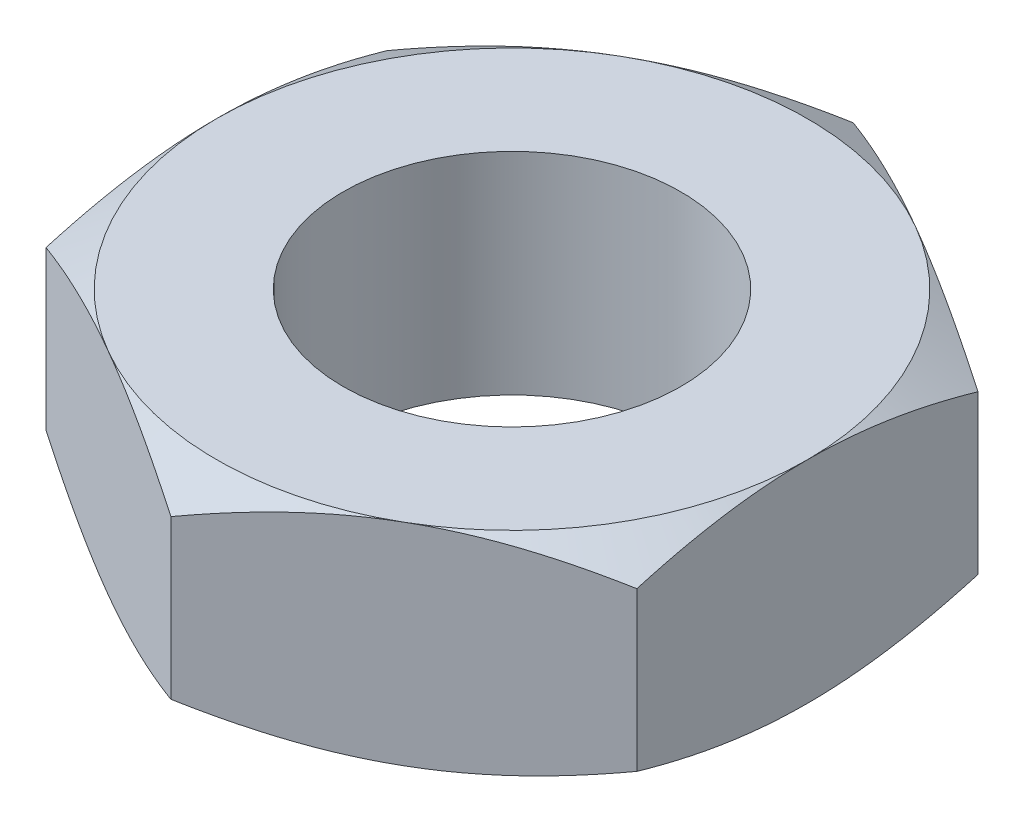
SolidWorks part; units mm, degrees
material "Alloy Steel"
ref_plane "Front Plane" through (0, 0, 0) normal (0, 0, 1) x (1, 0, 0)
ref_plane "Top Plane" through (0, 0, 0) normal (0, 1, 0) x (1, 0, 0)
ref_plane "Right Plane" through (0, 0, 0) normal (1, 0, 0) x (0, 0, -1)
sketch "Sketch1" plane through (0, 0, 0) normal (0, 1, 0) x (1, 0, 0)
  line L1 (-5.5563, 3.2079) -> (-5.5563, -3.2079)
  line L2 (-5.5563, -3.2079) -> (0, -6.4158)
  line L3 (0, -6.4158) -> (5.5562, -3.2079)
  line L4 (5.5562, -3.2079) -> (5.5562, 3.2079)
  line L5 (5.5562, 3.2079) -> (0, 6.4158)
  line L6 (0, 6.4158) -> (-5.5563, 3.2079)
  circle A0 centre (0, 0) radius 5.5563 construction
  circle A1 centre (0, 0) radius 3.175
  dimension "Thread Size" = 6.35
  dimension "Hex" = 11.1125
extrude "Boss-Extrude1" add sketch "Sketch1" along normal mid plane 3.9688
sketch "Sketch2" plane through (0, 1.9844, 0) normal (0, 1, 0) x (1, 0, 0)
  circle A0 centre (0, 0) radius 3.175 construction
  circle A1 centre (0, 0) radius 3.175
curve "Helix/Spiral1" [suppressed] pitch 0.9071 height 4.8759 turns 5.375 parameters "Pitch"=0.9071
sketch "Sketch3" plane through (0, 0, 0) normal (1, 0, 0) x (0, 0, -1)
  line L0 (2.5858, 2.4379) -> (3.175, 2.7781)
  line L1 (3.175, 2.7781) -> (3.175, 1.9844)
  line L2 (3.175, 1.9844) -> (2.5858, 2.3246)
  line L3 (2.5858, 2.3246) -> (2.5858, 2.4379)
  line L4 (2.8804, 2.608) -> (2.8804, 2.1545) construction
  line L5 (2.5858, 2.3812) -> (3.175, 2.3812) construction
  line L6 (3.175, 1.9844) -> (-3.175, 1.9844) construction
  dimension "D1" = 60
  dimension "D2" = 0.1134
  dimension "D3" = 0.4536
sweep "Sweep1" [suppressed] add profiles "Sketch3" path "Helix/Spiral1"
sketch "Sketch4" plane through (0, 1.9844, 0) normal (0, 1, 0) x (1, 0, 0)
  circle A1 centre (0, 0) radius 3.175
  circle A2 centre (0, 0) radius 3.175
  dimension "D1" = 0
extrude "Cut-Extrude1" [suppressed] cut sketch "Sketch4" along normal through all and the other way through all draft 45
sketch "Sketch5" plane through (0, 1.9844, 0) normal (0, 1, 0) x (1, 0, 0)
  circle A0 centre (0, 0) radius 5.5563 construction
  circle A1 centre (0, 0) radius 5.5563
extrude "Cut-Extrude2" cut sketch "Sketch5" against normal through all draft 60 flip side to cut
mirror "Mirror1" about plane through (0, 0, 0) normal (0, 1, 0) of "Cut-Extrude2", "Cut-Extrude1"
move or copy body "Body-Move/Copy1" [suppressed] bodies to move or copy 105 parameters "D1"=0, "D2"=0, "D3"=0
move or copy body "Body-Move/Copy2" [suppressed] bodies to move or copy 106 parameters "D1"=0, "D2"=0, "D3"=0
move or copy body "Body-Move/Copy3" [suppressed] bodies to move or copy 107 parameters "D1"=0, "D2"=0, "D3"=0
move or copy body "Body-Move/Copy4" [suppressed] bodies to move or copy 108 parameters "D1"=0, "D2"=0, "D3"=0
equation "\"D2@Sketch3\" = \"Pitch@Helix/Spiral1\"*.125"
equation "\"D3@Sketch3\" = \"Pitch@Helix/Spiral1\"*.5"
equation "\"D3@Helix/Spiral1\" = \"Height@Boss-Extrude1\"+\"Pitch@Helix/Spiral1\""
